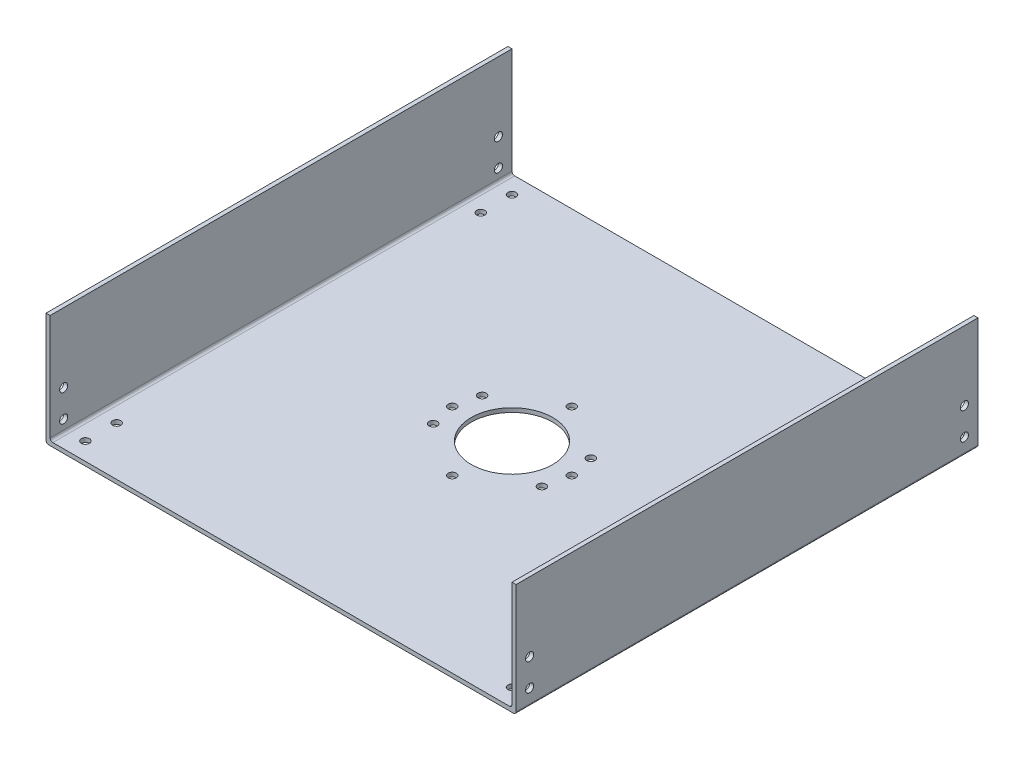
SolidWorks part; units mm, degrees
ref_plane "Front Plane" through (0, 0, 0) normal (0, 0, 1) x (1, 0, 0)
ref_plane "Top Plane" through (0, 0, 0) normal (0, 1, 0) x (1, 0, 0)
ref_plane "Right Plane" through (0, 0, 0) normal (1, 0, 0) x (0, 0, -1)
sketch "Sketch2" plane through (0, 0, 0) normal (0, 1, 0) x (1, 0, 0)
  line L1 (0, 0) -> (170, 0)
  line L2 (0, 0) -> (0, 170)
  line L3 (0, 170) -> (170, 170)
  line L4 (170, 0) -> (170, 170)
  circle A0 centre (63, 85) radius 1.5
  circle A1 centre (85, 63) radius 1.5
  circle A2 centre (85, 107) radius 1.5
  circle A3 centre (107, 85) radius 1.5
  dimension "D1" = 170
  dimension "D2" = 170
extrude "Boss-Extrude1" add sketch "Sketch2" along normal blind 1.5
sketch "Sketch5" plane through (0, 1.5, 0) normal (0, 1, 0) x (1, 0, 0)
  line L1 (0, 0) -> (170, 0) construction
  line L2 (0, 170) -> (0, 0) construction
  circle A0 centre (85, 85) radius 15
  dimension "D1" = 30
  dimension "D2" = 85
  dimension "D3" = 85
extrude "Cut-Extrude1" cut sketch "Sketch5" against normal blind 5 and the other way blind 5 contours A0
sketch "Sketch6" plane through (0, 1.5, 0) normal (0, 1, 0) x (1, 0, 0)
  line L0 (0, 0) -> (170, 0) construction
  line L1 (0, 170) -> (0, 0) construction
  line L2 (170, 170) -> (0, 170) construction
  circle A0 centre (65, 94) radius 1.5
  circle A1 centre (65, 76) radius 1.5
  circle A2 centre (105, 76) radius 1.5
  circle A3 centre (105, 94) radius 1.5
  dimension "D1" = 65
  dimension "D2" = 65
  dimension "D3" = 76
  dimension "D4" = 76
extrude "Cut-Extrude2" cut sketch "Sketch6" against normal blind 5 and the other way blind 5
sketch "Sketch7" plane through (0, 1.5, 0) normal (0, 1, 0) x (1, 0, 0)
  line L0 (0, 0) -> (170, 0) construction
  line L2 (170, 170) -> (0, 170) construction
  line L8 (170, 0) -> (170, 170) construction
  line L9 (0, 170) -> (0, 0) construction
  circle A0 centre (6.5, 163.5) radius 1.5
  circle A1 centre (163.5, 163.5) radius 1.5
  circle A2 centre (163.5, 6.5) radius 1.5
  circle A3 centre (6.5, 6.5) radius 1.5
  dimension "D1" = 6.5
  dimension "D2" = 6.5
  dimension "D3" = 6.5
  dimension "D4" = 6.5
  dimension "D5" = 6.5
  dimension "D6" = 6.5
  dimension "D7" = 6.5
  dimension "D8" = 6.5
extrude "Cut-Extrude3" cut sketch "Sketch7" against normal blind 5 and the other way blind 5
sketch "Sketch8" plane through (0, 1.5, 0) normal (0, 1, 0) x (1, 0, 0)
  line L0 (170, 0) -> (170, 170) construction
  line L1 (0, 0) -> (170, 0) construction
  circle A0 centre (163.5, 18) radius 1.5
  circle A1 centre (163.5, 152) radius 1.5
  circle A2 centre (6.5, 152) radius 1.5
  circle A3 centre (6.5, 18) radius 1.5
  dimension "D1" = 6.5
  dimension "D2" = 18
extrude "Cut-Extrude4" cut sketch "Sketch8" against normal blind 10 and the other way blind 10
sketch "Sketch9" plane through (170, 0, 0) normal (1, 0, 0) x (0, 0, -1)
  line L1 (0, 0) -> (170, 0)
  line L2 (0, 0) -> (0, 41.5)
  line L3 (0, 41.5) -> (170, 41.5)
  line L4 (170, 0) -> (170, 41.5)
  dimension "D1" = 41.5
  dimension "D2" = 170
extrude "Boss-Extrude2" add sketch "Sketch9" along normal blind 1.5
sketch "Sketch14" plane through (171.5, 0, 0) normal (1, 0, 0) x (0, 0, -1)
  line L0 (170, 0) -> (170, 41.5) construction
  line L1 (0, 0) -> (170, 0) construction
  line L2 (0, 41.5) -> (0, 0) construction
  circle A0 centre (5, 15) radius 1.5
  circle A1 centre (5, 5) radius 1.5
  circle A2 centre (165, 15) radius 1.5
  circle A3 centre (165, 5) radius 1.5
  dimension "D1" = 10
  dimension "D2" = 5
  dimension "D3" = 5
  dimension "D4" = 5
  dimension "D5" = 5
  dimension "D6" = 5
  dimension "D7" = 10
  dimension "D8" = 5
fillet "Fillet2" radius 1 1 edges
fillet "Fillet3" radius 1 1 edges at (171.5, 0, -85)
sketch "Sketch10" plane through (0, 0, 0) normal (-1, 0, 0) x (0, 0, 1)
  line L1 (-170, 0) -> (0, 0)
  line L2 (-170, 0) -> (-170, 41.5)
  line L3 (-170, 41.5) -> (0, 41.5)
  line L4 (0, 0) -> (0, 41.5)
  dimension "D1" = 41.5
  dimension "D2" = 170
extrude "Boss-Extrude3" add sketch "Sketch10" along normal blind 1.5
fillet "Fillet4" radius 1 1 edges
fillet "Fillet5" radius 1 1 edges at (-1.5, 0, -85)
sketch "Sketch15" plane through (-1.5, 0, 0) normal (-1, 0, 0) x (0, 0, 1)
  line L0 (-170, 41.5) -> (-170, 1) construction
  line L1 (-170, 1) -> (0, 1) construction
  line L3 (0, 1) -> (0, 41.5) construction
  circle A0 centre (-165, 16) radius 1.5
  circle A1 centre (-165, 6) radius 1.5
  circle A2 centre (-5, 16) radius 1.5
  circle A3 centre (-5, 6) radius 1.5
  dimension "D1" = 5
  dimension "D2" = 5
  dimension "D3" = 10
  dimension "D4" = 5
  dimension "D5" = 5
  dimension "D6" = 5
  dimension "D7" = 10
  dimension "D8" = 5
extrude "Cut-Extrude6" cut sketch "Sketch15" against normal blind 10000 and the other way blind 10000
